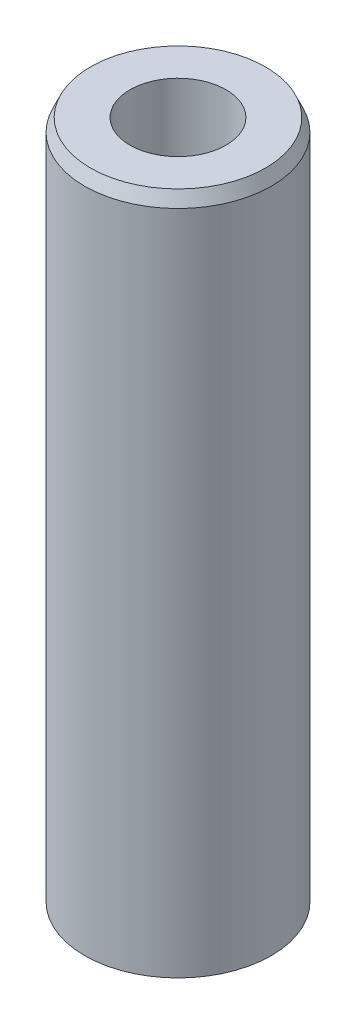
SolidWorks part; units mm, degrees
ref_plane "Front Plane" through (0, 0, 0) normal (0, 0, 1) x (1, 0, 0)
ref_plane "Top Plane" through (0, 0, 0) normal (0, 1, 0) x (1, 0, 0)
ref_plane "Right Plane" through (0, 0, 0) normal (1, 0, 0) x (0, 0, -1)
sketch "Sketch1" plane through (0, 0, 0) normal (0, 1, 0) x (1, 0, 0)
  circle A0 centre (0, 0) radius 5
  dimension "SHAFT_OD" = 10
extrude "Boss-Extrude1" add sketch "Sketch1" along normal blind 36.699
sketch "Sketch2" plane through (0, 0, 0) normal (0, 1, 0) x (1, 0, 0)
  circle A0 centre (0, 0) radius 2.5744
  dimension "BORE_D" = 5.1488
extrude "Cut-Extrude1" cut sketch "Sketch2" along normal through all
chamfer "Chamfer1" distance 0.6914 angle 23.998 2 edges at (0, 36.699, 5) (0, 0, 5) first distance on face at (0, 36.699, 5) first distance on face at (0, 0, 2.5744)
